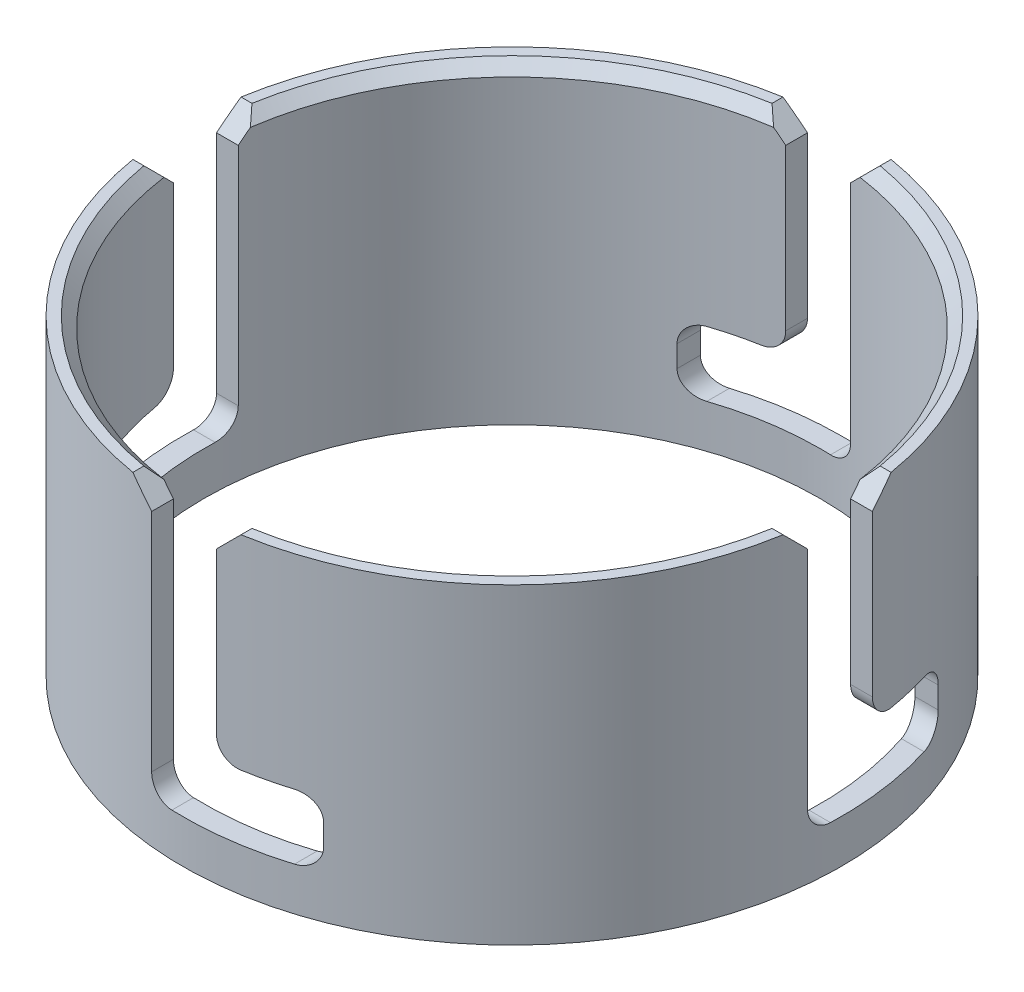
SolidWorks part; units mm, degrees
material "Plain Carbon Steel"
ref_plane "Front Plane" through (0, 0, 0) normal (0, 0, 1) x (1, 0, 0)
ref_plane "Top Plane" through (0, 0, 0) normal (0, 1, 0) x (1, 0, 0)
ref_plane "Right Plane" through (0, 0, 0) normal (1, 0, 0) x (0, 0, -1)
sketch "Sketch2" plane through (0, 0, 0) normal (1, 0, 0) x (0, 0, -1)
  line L0 (-71.2, 0) -> (-76.2, 0)
  line L1 (-76.2, 0) -> (-76.2, 72.15)
  line L2 (-76.2, 72.15) -> (-71.2, 72.15)
  line L5 (-71.2, 72.15) -> (-71.2, 0)
  dimension "D1" = 76.2
  dimension "D2" = 72.15
  dimension "D3" = 5
ref_axis "Axis1" through (0, -3.6075, 0) along (0, 1, 0)
revolve "Revolve1" add sketch "Sketch2" angle 360 about axis through (0, -3.6075, 0) along (0, 1, 0)
sketch "Sketch3" plane through (0, 0, 0) normal (1, 0, 0) x (0, 0, -1)
  line L0 (-7.5, 72.15) -> (7.5, 72.15)
  line L1 (76.2, 72.15) -> (-76.2, 72.15) construction
  line L2 (7.5, 72.15) -> (7.5, 10)
  line L3 (7.5, 10) -> (-27.5, 10)
  line L4 (-27.5, 10) -> (-27.5, 25)
  line L5 (-27.5, 25) -> (-7.5, 25)
  line L6 (-7.5, 25) -> (-7.5, 72.15)
  line L7 (0, -3.6075) -> (0, 75.7575) construction
  line L8 (0, 0) -> (0, 47.5309) construction
  line L9 (-76.2, 0) -> (76.2, 0) construction
  dimension "D1" = 10
  dimension "D2" = 15
  dimension "D3" = 15
  dimension "D4" = 20
extrude "Cut-Extrude1" cut sketch "Sketch3" against normal through all
fillet "Fillet1" radius 5 2 edges at (-73.3169, 25, 7.5) (-73.3169, 10, -7.5)
chamfer "Chamfer1" distance 5 angle 45 2 edges at (-73.3169, 72.15, 7.5) (-73.3169, 72.15, -7.5)
fillet "Fillet3" radius 5 2 edges at (-68.3698, 25, 27.5) (-68.3698, 10, 27.5)
pattern_circular "CirPattern1" count 4 over 360 about axis through (0, -3.6075, 0) along (0, 1, 0) of "Fillet3", "Chamfer1", "Fillet1", "Cut-Extrude1"
chamfer "Chamfer2" distance 2.5 angle 45 4 edges at (-50.346, 72.15, -50.346) (50.346, 72.15, -50.346) (50.346, 72.15, 50.346) (-50.346, 72.15, 50.346)
equation "\"TubeDiameter\"= 6.000in"
equation "\"D1@Sketch2\"=\"TubeDiameter\"/2"
